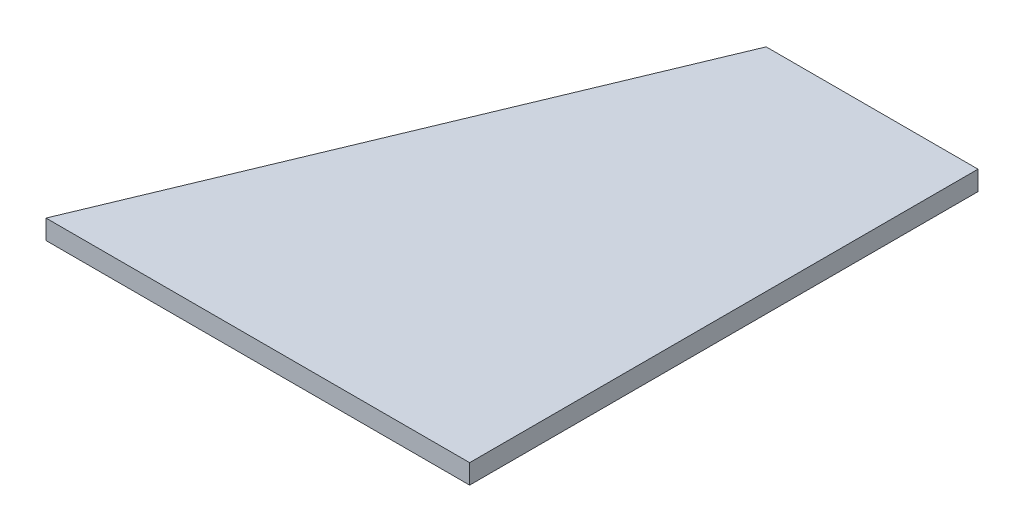
SolidWorks part; units mm, degrees
ref_plane "Front Plane" through (0, 0, 0) normal (0, 0, 1) x (1, 0, 0)
ref_plane "Top Plane" through (0, 0, 0) normal (0, 1, 0) x (1, 0, 0)
ref_plane "Right Plane" through (0, 0, 0) normal (1, 0, 0) x (0, 0, -1)
sketch "Sketch1" plane through (0, 0, 0) normal (0, 1, 0) x (1, 0, 0)
  line L1 (0, 0) -> (-304.8, 0)
  line L2 (0, 0) -> (0, 76.2)
  line L3 (0, 76.2) -> (-304.8, 76.2)
  line L4 (-304.8, 0) -> (-304.8, 76.2)
  dimension "D1" = 304.8
  dimension "D2" = 76.2
extrude "Boss-Extrude1" add sketch "Sketch1" along normal blind 3.175
sketch "Sketch2" plane through (0, 3.175, 0) normal (0, 1, 0) x (1, 0, 0)
  line L0 (-304.8, 76.2) -> (-304.8, 0) construction
  line L1 (-304.8, 6.35) -> (-215.9, 6.35) construction
  line L2 (-304.8, 6.35) -> (-304.8, 0) construction
  line L3 (-304.8, 0) -> (-215.9, 0) construction
  line L4 (-215.9, 6.35) -> (-215.9, 0) construction
  line L5 (-304.8, 0) -> (0, 0) construction
  line L6 (-304.8, 6.35) -> (-311.15, 6.35) construction
  line L7 (-311.15, 6.35) -> (-311.15, 0) construction
  line L8 (-311.15, 0) -> (-304.8, 0) construction
  line L9 (-215.9, 6.35) -> (-209.55, 6.35) construction
  line L10 (-209.55, 6.35) -> (-209.55, 0) construction
  line L11 (-209.55, 0) -> (-215.9, 0) construction
  line L12 (-304.8, 5.1324) -> (-304.8, 0.3904)
  line L13 (-215.9, 0.2103) -> (-215.9, 6.35)
  line L14 (-301.1367, 0) -> (-217.3799, 0)
  line L15 (-304.7482, 14.32) -> (-304.7482, 9.5781)
  line L16 (-215.8482, 9.3979) -> (-215.8482, 15.5376)
  line L17 (-301.0849, 9.1876) -> (-217.3281, 9.1876)
  line L18 (-304.7756, 23.4355) -> (-304.7756, 18.6936)
  line L19 (-215.8756, 18.5134) -> (-215.8756, 24.6532)
  line L20 (-301.1123, 18.3032) -> (-217.3555, 18.3032)
  line L21 (-304.7238, 32.6232) -> (-304.7238, 27.8813)
  line L22 (-215.8238, 27.7011) -> (-215.8238, 33.8408)
  line L23 (-301.0605, 27.4908) -> (-217.3037, 27.4908)
  line L24 (-304.6921, 41.752) -> (-304.6921, 37.0101)
  line L25 (-215.7921, 36.8299) -> (-215.7921, 42.9697)
  line L26 (-301.0288, 36.6197) -> (-217.272, 36.6197)
  line L27 (-304.6403, 50.9397) -> (-304.6403, 46.1977)
  line L28 (-215.7403, 46.0176) -> (-215.7403, 52.1573)
  line L29 (-300.977, 45.8073) -> (-217.2202, 45.8073)
  line L30 (-304.6677, 60.0552) -> (-304.6677, 55.3133)
  line L31 (-215.7677, 55.1331) -> (-215.7677, 61.2729)
  line L32 (-301.0044, 54.9229) -> (-217.2476, 54.9229)
  line L33 (-304.6159, 69.2428) -> (-304.6159, 64.5009)
  line L34 (-215.7159, 64.3207) -> (-215.7159, 70.4605)
  line L35 (-300.9526, 64.1105) -> (-217.1958, 64.1105)
  line L36 (-215.1839, 5.3155) -> (-215.1839, 0.5736)
  line L37 (-126.2839, 0.3934) -> (-126.2839, 6.5331)
  line L38 (-211.5206, 0.1831) -> (-127.7637, 0.1831)
  line L39 (-215.1321, 14.5031) -> (-215.1321, 9.7612)
  line L40 (-126.2321, 9.581) -> (-126.2321, 15.7207)
  line L41 (-211.4688, 9.3707) -> (-127.7119, 9.3707)
  line L42 (-215.1595, 23.6187) -> (-215.1595, 18.8768)
  line L43 (-126.2595, 18.6966) -> (-126.2595, 24.8363)
  line L44 (-211.4962, 18.4863) -> (-127.7393, 18.4863)
  line L45 (-215.1077, 32.8063) -> (-215.1077, 28.0644)
  line L46 (-126.2077, 27.8842) -> (-126.2077, 34.0239)
  line L47 (-211.4444, 27.6739) -> (-127.6875, 27.6739)
  spline S0 degree 3 poles (-304.8, 5.1324) (-295.0561, 7.9134) (-284.6351, 9.1758) (-256.6545, 7.9107) (-231.9837, 8.0391) (-215.9, 6.35) knots 0.033342 0.033342 0.033342 0.033342 0.196819 0.285044 0.915588 0.915588 0.915588 0.915588
  spline S1 degree 3 poles (-304.8, 0.3904) (-303.8212, 0.2292) (-302.6326, 0.1002) (-301.1367, 0) knots 0.767988 0.767988 0.767988 0.767988 1 1 1 1
  spline S2 degree 2 poles (-215.9, 0.2103) (-216.6026, 0.0759) (-217.3799, 0) knots 0.882957 0.882957 0.882957 1 1 1
  spline S3 degree 3 poles (-304.7482, 14.32) (-295.0043, 17.101) (-284.5833, 18.3634) (-256.6027, 17.0983) (-231.9319, 17.2267) (-215.8482, 15.5376) knots 0.033342 0.033342 0.033342 0.033342 0.196819 0.285044 0.915588 0.915588 0.915588 0.915588
  spline S4 degree 3 poles (-304.7482, 9.5781) (-303.7694, 9.4169) (-302.5808, 9.2879) (-301.0849, 9.1876) knots 0.767988 0.767988 0.767988 0.767988 1 1 1 1
  spline S5 degree 2 poles (-215.8482, 9.3979) (-216.5508, 9.2635) (-217.3281, 9.1876) knots 0.882957 0.882957 0.882957 1 1 1
  spline S6 degree 3 poles (-304.7756, 23.4355) (-295.0317, 26.2166) (-284.6108, 27.479) (-256.6301, 26.2139) (-231.9593, 26.3423) (-215.8756, 24.6532) knots 0.033342 0.033342 0.033342 0.033342 0.196819 0.285044 0.915588 0.915588 0.915588 0.915588
  spline S7 degree 3 poles (-304.7756, 18.6936) (-303.7969, 18.5324) (-302.6082, 18.4034) (-301.1123, 18.3032) knots 0.767988 0.767988 0.767988 0.767988 1 1 1 1
  spline S8 degree 2 poles (-215.8756, 18.5134) (-216.5782, 18.3791) (-217.3555, 18.3032) knots 0.882957 0.882957 0.882957 1 1 1
  spline S9 degree 3 poles (-304.7238, 32.6232) (-294.9799, 35.4042) (-284.5589, 36.6666) (-256.5783, 35.4015) (-231.9075, 35.5299) (-215.8238, 33.8408) knots 0.033342 0.033342 0.033342 0.033342 0.196819 0.285044 0.915588 0.915588 0.915588 0.915588
  spline S10 degree 3 poles (-304.7238, 27.8813) (-303.745, 27.72) (-302.5564, 27.591) (-301.0605, 27.4908) knots 0.767988 0.767988 0.767988 0.767988 1 1 1 1
  spline S11 degree 2 poles (-215.8238, 27.7011) (-216.5264, 27.5667) (-217.3037, 27.4908) knots 0.882957 0.882957 0.882957 1 1 1
  spline S12 degree 3 poles (-304.6921, 41.752) (-294.9482, 44.5331) (-284.5273, 45.7954) (-256.5466, 44.5304) (-231.8758, 44.6587) (-215.7921, 42.9697) knots 0.033342 0.033342 0.033342 0.033342 0.196819 0.285044 0.915588 0.915588 0.915588 0.915588
  spline S13 degree 3 poles (-304.6921, 37.0101) (-303.7134, 36.8489) (-302.5247, 36.7199) (-301.0288, 36.6197) knots 0.767988 0.767988 0.767988 0.767988 1 1 1 1
  spline S14 degree 2 poles (-215.7921, 36.8299) (-216.4947, 36.6956) (-217.272, 36.6197) knots 0.882957 0.882957 0.882957 1 1 1
  spline S15 degree 3 poles (-304.6403, 50.9397) (-294.8964, 53.7207) (-284.4755, 54.9831) (-256.4948, 53.718) (-231.824, 53.8464) (-215.7403, 52.1573) knots 0.033342 0.033342 0.033342 0.033342 0.196819 0.285044 0.915588 0.915588 0.915588 0.915588
  spline S16 degree 3 poles (-304.6403, 46.1977) (-303.6616, 46.0365) (-302.4729, 45.9075) (-300.977, 45.8073) knots 0.767988 0.767988 0.767988 0.767988 1 1 1 1
  spline S17 degree 2 poles (-215.7403, 46.0176) (-216.4429, 45.8832) (-217.2202, 45.8073) knots 0.882957 0.882957 0.882957 1 1 1
  spline S18 degree 3 poles (-304.6677, 60.0552) (-294.9238, 62.8363) (-284.5029, 64.0986) (-256.5222, 62.8336) (-231.8514, 62.9619) (-215.7677, 61.2729) knots 0.033342 0.033342 0.033342 0.033342 0.196819 0.285044 0.915588 0.915588 0.915588 0.915588
  spline S19 degree 3 poles (-304.6677, 55.3133) (-303.689, 55.1521) (-302.5003, 55.0231) (-301.0044, 54.9229) knots 0.767988 0.767988 0.767988 0.767988 1 1 1 1
  spline S20 degree 2 poles (-215.7677, 55.1331) (-216.4703, 54.9988) (-217.2476, 54.9229) knots 0.882957 0.882957 0.882957 1 1 1
  spline S21 degree 3 poles (-304.6159, 69.2428) (-294.872, 72.0239) (-284.4511, 73.2863) (-256.4704, 72.0212) (-231.7996, 72.1496) (-215.7159, 70.4605) knots 0.033342 0.033342 0.033342 0.033342 0.196819 0.285044 0.915588 0.915588 0.915588 0.915588
  spline S22 degree 3 poles (-304.6159, 64.5009) (-303.6372, 64.3397) (-302.4485, 64.2107) (-300.9526, 64.1105) knots 0.767988 0.767988 0.767988 0.767988 1 1 1 1
  spline S23 degree 2 poles (-215.7159, 64.3207) (-216.4185, 64.1864) (-217.1958, 64.1105) knots 0.882957 0.882957 0.882957 1 1 1
  spline S24 degree 3 poles (-215.1839, 5.3155) (-205.4399, 8.0965) (-195.019, 9.3589) (-167.0384, 8.0938) (-142.3676, 8.2222) (-126.2839, 6.5331) knots 0.033342 0.033342 0.033342 0.033342 0.196819 0.285044 0.915588 0.915588 0.915588 0.915588
  spline S25 degree 3 poles (-215.1839, 0.5736) (-214.2051, 0.4124) (-213.0165, 0.2834) (-211.5206, 0.1831) knots 0.767988 0.767988 0.767988 0.767988 1 1 1 1
  spline S26 degree 2 poles (-126.2839, 0.3934) (-126.9865, 0.2591) (-127.7637, 0.1831) knots 0.882957 0.882957 0.882957 1 1 1
  spline S27 degree 3 poles (-215.1321, 14.5031) (-205.3881, 17.2842) (-194.9672, 18.5465) (-166.9866, 17.2815) (-142.3158, 17.4098) (-126.2321, 15.7207) knots 0.033342 0.033342 0.033342 0.033342 0.196819 0.285044 0.915588 0.915588 0.915588 0.915588
  spline S28 degree 3 poles (-215.1321, 9.7612) (-214.1533, 9.6) (-212.9646, 9.471) (-211.4688, 9.3707) knots 0.767988 0.767988 0.767988 0.767988 1 1 1 1
  spline S29 degree 2 poles (-126.2321, 9.581) (-126.9347, 9.4467) (-127.7119, 9.3707) knots 0.882957 0.882957 0.882957 1 1 1
  spline S30 degree 3 poles (-215.1595, 23.6187) (-205.4155, 26.3997) (-194.9946, 27.6621) (-167.014, 26.397) (-142.3432, 26.5254) (-126.2595, 24.8363) knots 0.033342 0.033342 0.033342 0.033342 0.196819 0.285044 0.915588 0.915588 0.915588 0.915588
  spline S31 degree 3 poles (-215.1595, 18.8768) (-214.1807, 18.7155) (-212.9921, 18.5866) (-211.4962, 18.4863) knots 0.767988 0.767988 0.767988 0.767988 1 1 1 1
  spline S32 degree 2 poles (-126.2595, 18.6966) (-126.9621, 18.5622) (-127.7393, 18.4863) knots 0.882957 0.882957 0.882957 1 1 1
  spline S33 degree 3 poles (-215.1077, 32.8063) (-205.3637, 35.5874) (-194.9428, 36.8497) (-166.9622, 35.5847) (-142.2914, 35.713) (-126.2077, 34.0239) knots 0.033342 0.033342 0.033342 0.033342 0.196819 0.285044 0.915588 0.915588 0.915588 0.915588
  spline S34 degree 3 poles (-215.1077, 28.0644) (-214.1289, 27.9032) (-212.9403, 27.7742) (-211.4444, 27.6739) knots 0.767988 0.767988 0.767988 0.767988 1 1 1 1
  spline S35 degree 2 poles (-126.2077, 27.8842) (-126.9103, 27.7499) (-127.6875, 27.6739) knots 0.882957 0.882957 0.882957 1 1 1
  dimension "D1" = 88.9
  dimension "D2" = 6.35
  dimension "D3" = 6.35
  dimension "D4" = 6.35
  dimension "D5" = 2.54
  dimension "D6" = 30.48
extrude "Cut-Extrude3" cut sketch "Sketch2" against normal blind 0.254
sketch "Sketch3" plane through (0, 3.175, 0) normal (0, 1, 0) x (1, 0, 0)
  line L0 (-217.3799, 0) -> (0, 0) construction
  line L1 (-124.7737, 0) -> (-73.9737, 0)
  line L2 (-124.7737, 0) -> (-124.7737, 5.588)
  line L4 (-73.9737, 0) -> (-73.9737, 5.715)
  line L5 (-124.6661, 9.5552) -> (-73.8661, 9.5552)
  line L6 (-124.6661, 9.5552) -> (-124.6661, 15.1432)
  line L7 (-73.8661, 9.5552) -> (-73.8661, 15.2702)
  line L12 (-124.6047, 19.1295) -> (-73.8047, 19.1295)
  line L13 (-124.6047, 19.1295) -> (-124.6047, 24.7175)
  line L14 (-73.8047, 19.1295) -> (-73.8047, 24.8445)
  line L17 (-124.4952, 28.7633) -> (-73.6952, 28.7633)
  line L18 (-124.4952, 28.7633) -> (-124.4952, 34.3513)
  line L19 (-73.6952, 28.7633) -> (-73.6952, 34.4783)
  line L22 (-124.3858, 38.3971) -> (-73.5858, 38.3971)
  line L23 (-124.3858, 38.3971) -> (-124.3858, 43.9851)
  line L24 (-73.5858, 38.3971) -> (-73.5858, 44.1121)
  line L27 (-124.1668, 49.2351) -> (-73.3668, 49.2351)
  line L28 (-124.1668, 49.2351) -> (-124.1668, 54.8231)
  line L29 (-73.3668, 49.2351) -> (-73.3668, 54.9501)
  line L32 (-124.1389, 59.0137) -> (-73.3389, 59.0137)
  line L33 (-124.1389, 59.0137) -> (-124.1389, 64.6017)
  line L34 (-73.3389, 59.0137) -> (-73.3389, 64.7287)
  line L37 (-213.6694, 38.4491) -> (-162.8694, 38.4491)
  line L38 (-213.6694, 38.4491) -> (-213.6694, 44.0371)
  line L39 (-162.8694, 38.4491) -> (-162.8694, 44.1641)
  line L42 (-213.513, 49.2396) -> (-162.713, 49.2396)
  line L43 (-213.513, 49.2396) -> (-213.513, 54.8276)
  line L44 (-162.713, 49.2396) -> (-162.713, 54.9546)
  line L47 (-213.2002, 60.0302) -> (-162.4002, 60.0302)
  line L48 (-213.2002, 60.0302) -> (-213.2002, 65.6182)
  line L49 (-162.4002, 60.0302) -> (-162.4002, 65.7452)
  line L52 (0, 76.2) -> (-31.75, 76.2)
  line L53 (0, 76.2) -> (-304.8, 76.2) construction
  line L54 (-31.75, 76.2) -> (-63.5, 0)
  line L55 (-63.5, 0) -> (0, 0)
  line L56 (0, 0) -> (0, 76.2)
  spline S0 degree 2 poles (-124.7737, 5.588) (-99.3908, 12.6276) (-73.9737, 5.715) knots 0 0 0 1 1 1
  spline S1 degree 2 poles (-124.6661, 15.1432) (-99.282, 21.6837) (-73.8661, 15.2702) knots 0 0 0 1 1 1
  spline S2 degree 2 poles (-124.6047, 24.7175) (-99.2206, 31.2579) (-73.8047, 24.8445) knots 0 0 0 1 1 1
  spline S3 degree 2 poles (-124.4952, 34.3513) (-99.1112, 40.8917) (-73.6952, 34.4783) knots 0 0 0 1 1 1
  spline S4 degree 2 poles (-124.3858, 43.9851) (-99.0017, 50.5255) (-73.5858, 44.1121) knots 0 0 0 1 1 1
  spline S5 degree 2 poles (-124.1668, 54.8231) (-98.7827, 61.3635) (-73.3668, 54.9501) knots 0 0 0 1 1 1
  spline S6 degree 2 poles (-124.1389, 64.6017) (-98.7548, 71.1422) (-73.3389, 64.7287) knots 0 0 0 1 1 1
  spline S7 degree 2 poles (-213.6694, 44.0371) (-188.2853, 50.5775) (-162.8694, 44.1641) knots 0 0 0 1 1 1
  spline S8 degree 2 poles (-213.513, 54.8276) (-188.1289, 61.3681) (-162.713, 54.9546) knots 0 0 0 1 1 1
  spline S9 degree 2 poles (-213.2002, 65.6182) (-187.8162, 72.1587) (-162.4002, 65.7452) knots 0 0 0 1 1 1
  dimension "D1" = 5.588
  dimension "D2" = 5.715
  dimension "D3" = 5.588
  dimension "D4" = 5.715
  dimension "D5" = 5.588
  dimension "D6" = 5.715
  dimension "D7" = 5.588
  dimension "D8" = 5.715
  dimension "D9" = 5.588
  dimension "D10" = 5.715
  dimension "D11" = 5.588
  dimension "D12" = 5.715
  dimension "D13" = 5.588
  dimension "D14" = 5.715
  dimension "D15" = 5.588
  dimension "D16" = 5.715
  dimension "D17" = 5.588
  dimension "D18" = 5.715
  dimension "D19" = 5.588
  dimension "D20" = 5.715
  dimension "D21" = 31.75
  dimension "D22" = 63.5
extrude "Cut-Extrude5" cut sketch "Sketch3" against normal blind 0.254
extrude "Cut-Extrude9" cut sketch "Sketch3<3>" against normal through all flip side to cut contours L55 L56 L52 L54 region at (-24.6944, 3.175, -33.8667)
sketch "Sketch3<3>" plane through (0, 3.175, 0) normal (0, 1, 0) x (1, 0, 0) same geometry as "Sketch3"
